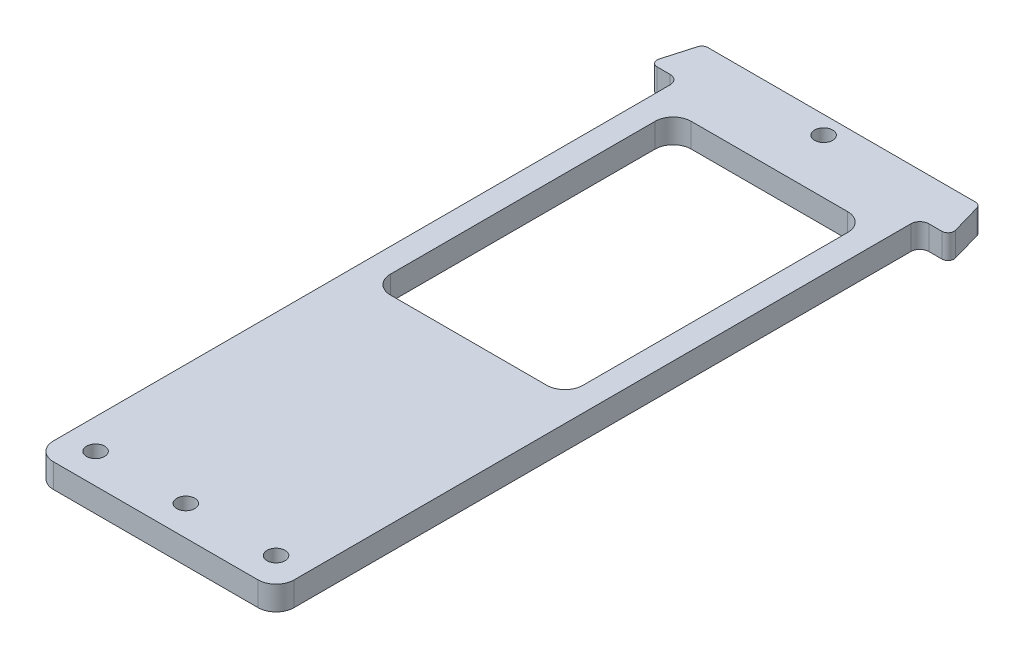
SolidWorks part; units mm, degrees
material "1060 Alloy"
ref_plane "Front Plane" through (0, 0, 0) normal (0, 0, 1) x (1, 0, 0)
ref_plane "Top Plane" through (0, 0, 0) normal (0, 1, 0) x (1, 0, 0)
ref_plane "Right Plane" through (0, 0, 0) normal (1, 0, 0) x (0, 0, -1)
sketch "Sketch1" plane through (0, 0, 0) normal (0, 1, 0) x (1, 0, 0)
  line L1 (0, 0) -> (40, 0)
  line L3 (0, 114) -> (40, 114)
  line L5 (4, 102) -> (36, 102)
  line L6 (4, 102) -> (4, 52)
  line L7 (4, 52) -> (36, 52)
  line L8 (36, 102) -> (36, 52)
  line L9 (40, 114) -> (40, 0)
  line L11 (0, 114) -> (0, 0)
  line L12 (20, 5) -> (20, 0) construction
  circle A0 centre (5, 5) radius 1.5
  circle A1 centre (35, 5) radius 1.5
  circle A2 centre (20, 5) radius 1.5
  circle A3 centre (20, 111) radius 1.5
  dimension "D7" = 3
  dimension "D12" = 3
  dimension "D2" = 32
  dimension "D3" = 50
  dimension "D4" = 4
  dimension "D5" = 12
  dimension "D6" = 52
  dimension "D8" = 5
  dimension "D9" = 5
  dimension "D10" = 5
  dimension "D14" = 4
  dimension "D15" = 3
  dimension "D16" = 20
extrude "Boss-Extrude1" add sketch "Sketch1" along normal blind 4
fillet "Fillet1" radius 3 4 edges at (36, 2, -52) (4, 2, -52) (36, 2, -102) (4, 2, -102)
sketch "Sketch2" plane through (0, 4, 0) normal (0, 1, 0) x (1, 0, 0)
  line L0 (0, 114) -> (-3, 114)
  line L1 (-3, 114) -> (-5, 107)
  line L2 (-5, 107) -> (0, 107)
  line L4 (0, 107) -> (0, 114)
  line L5 (40, 114) -> (43, 114)
  line L6 (43, 114) -> (45, 107)
  line L7 (45, 107) -> (40, 107)
  line L9 (40, 107) -> (40, 114)
  line L10 (40, 114) -> (0, 114) construction
  line L11 (0, 114) -> (0, 0) construction
  dimension "D1" = 7
  dimension "D2" = 5
  dimension "D3" = 3
extrude "Boss-Extrude2" add sketch "Sketch2" against normal up to surface (4 mm away) up to face at (20, 0, -3.5)
fillet "Fillet2" radius 1 4 edges at (43, 2, -114) (45, 2, -107) (-5, 2, -107) (-3, 2, -114)
fillet "Fillet4" radius 3 2 edges at (40, 2, 0) (0, 2, 0)
fillet "Fillet5" radius 1.5 2 edges
